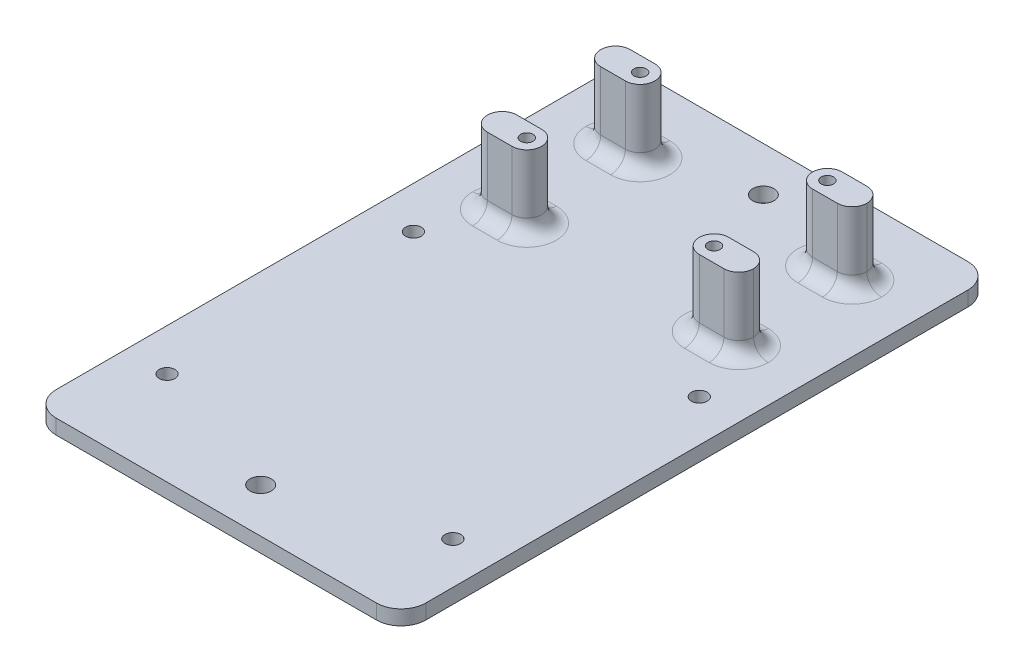
SolidWorks part; units mm, degrees
ref_plane "Front Plane" through (0, 0, 0) normal (0, 0, 1) x (1, 0, 0)
ref_plane "Top Plane" through (0, 0, 0) normal (0, 1, 0) x (1, 0, 0)
ref_plane "Right Plane" through (0, 0, 0) normal (1, 0, 0) x (0, 0, -1)
sketch "Sketch1" plane through (0, 0, 0) normal (0, 1, 0) x (1, 0, 0)
  line L0 (0, 60) -> (0, -60) construction
  line L1 (-32.5, 60) -> (32.5, 60)
  line L2 (-37.5, 55) -> (-37.5, -55)
  line L3 (-32.5, -60) -> (32.5, -60)
  line L4 (37.5, 55) -> (37.5, -55)
  line L5 (0, -51) -> (0, 51) construction
  line L6 (29, -41) -> (-29, -41) construction
  line L7 (19, 45) -> (-19, 45) construction
  line L8 (-19, 48) -> (-27, 48)
  line L9 (-27, 48) -> (-27, 42)
  line L10 (-27, 42) -> (-19, 42)
  line L11 (-19, 22) -> (-19, 45) construction
  line L12 (-29, 9) -> (-29, -41) construction
  line L13 (-19, 25) -> (-27, 25)
  line L14 (-27, 25) -> (-27, 19)
  line L15 (-27, 19) -> (-19, 19)
  line L16 (27, 19) -> (19, 19)
  line L17 (27, 25) -> (27, 19)
  line L18 (19, 25) -> (27, 25)
  line L19 (27, 42) -> (19, 42)
  line L20 (27, 48) -> (27, 42)
  line L21 (19, 48) -> (27, 48)
  circle A0 centre (0, 51) radius 2.15
  circle A1 centre (0, -51) radius 2.15
  arc A2 (32.5, 60) -> (37.5, 55) centre (32.5, 55) cw
  arc A3 (37.5, -55) -> (32.5, -60) centre (32.5, -55) cw
  arc A4 (-32.5, -60) -> (-37.5, -55) centre (-32.5, -55) cw
  arc A5 (-37.5, 55) -> (-32.5, 60) centre (-32.5, 55) cw
  circle A6 centre (-29, -41) radius 1.6
  circle A7 centre (29, -41) radius 1.6
  circle A8 centre (29, 9) radius 1.6
  circle A9 centre (-29, 9) radius 1.6
  circle A10 centre (-19, 45) radius 1.25
  circle A13 centre (-19, 22) radius 1.25
  arc A17 (-19, 42) -> (-19, 48) centre (-19, 45) ccw
  arc A18 (-19, 19) -> (-19, 25) centre (-19, 22) ccw
  circle A19 centre (19, 22) radius 1.25
  circle A20 centre (19, 45) radius 1.25
  arc A21 (19, 19) -> (19, 25) centre (19, 22) cw
  arc A22 (19, 42) -> (19, 48) centre (19, 45) cw
  point P6 (0, 0)
  point P12 (0, -41)
  point P31 (0, 45)
  dimension "D1" = 4.3
  dimension "D2" = 4.3
  dimension "D6" = 5
  dimension "D7" = 3.2
  dimension "D11" = 2.5
  dimension "D15" = 6
  dimension "D16" = 8
  dimension "D17" = 38
  dimension "D18" = 23
  dimension "D3" = 102
  dimension "D4" = 120
  dimension "D5" = 75
  dimension "D10" = 10
  dimension "D14" = 6
  dimension "D19" = 50
  dimension "D20" = 58
  dimension "D8" = 2
  dimension "D9" = 2
  dimension "D12" = 1
  dimension "D13" = 2
extrude "Boss-Extrude1" add sketch "Sketch1" against normal blind 3 contours L4 A3 L3 A4 L2 A5 L1 A2
extrude "Cut-Extrude1" cut sketch "Sketch1<3>" against normal through all contours A9 | A13 | A10 | A0 | A20 | A19 | A8 | A7 | A1 | A6
sketch "Sketch1<3>" plane through (0, 0, 0) normal (0, 1, 0) x (1, 0, 0) same geometry as "Sketch1"
extrude "Boss-Extrude2" add sketch "Sketch1<4>" along normal blind 15 contours L10 A17 L8 L9 A10 | L15 A18 L13 L14 A13 | A21 L16 L17 L18 A19 | A22 L19 L20 L21 A20 region at (-22.0404, 0, -45) region at (-22.0404, 0, -22) region at (22.0404, 0, -22) region at (22.0404, 0, -45)
sketch "Sketch1<4>" plane through (0, 0, 0) normal (0, 1, 0) x (1, 0, 0) same geometry as "Sketch1"
fillet "Fillet2" radius 3 8 edges at (-27, 7.5, -48) (-27, 7.5, -42) (-27, 7.5, -25) (-27, 7.5, -19) (27, 7.5, -19) (27, 7.5, -25) (27, 7.5, -48) (27, 7.5, -42)
fillet "Fillet1" radius 3 20 edges at (21.5, 0, -42) (21.5, 0, -48) (-21.5, 0, -42) (-21.5, 0, -48) (21.5, 0, -19) (21.5, 0, -25) (-21.5, 0, -19) (-21.5, 0, -25) (16, 0, -45) (-16, 0, -45) (16, 0, -22) (-16, 0, -22) (26.1213, 0, -42.8787) (26.1213, 0, -47.1213) (-26.1213, 0, -42.8787) (-26.1213, 0, -47.1213) (26.1213, 0, -19.8787) (26.1213, 0, -24.1213) (-26.1213, 0, -19.8787) (-26.1213, 0, -24.1213)
